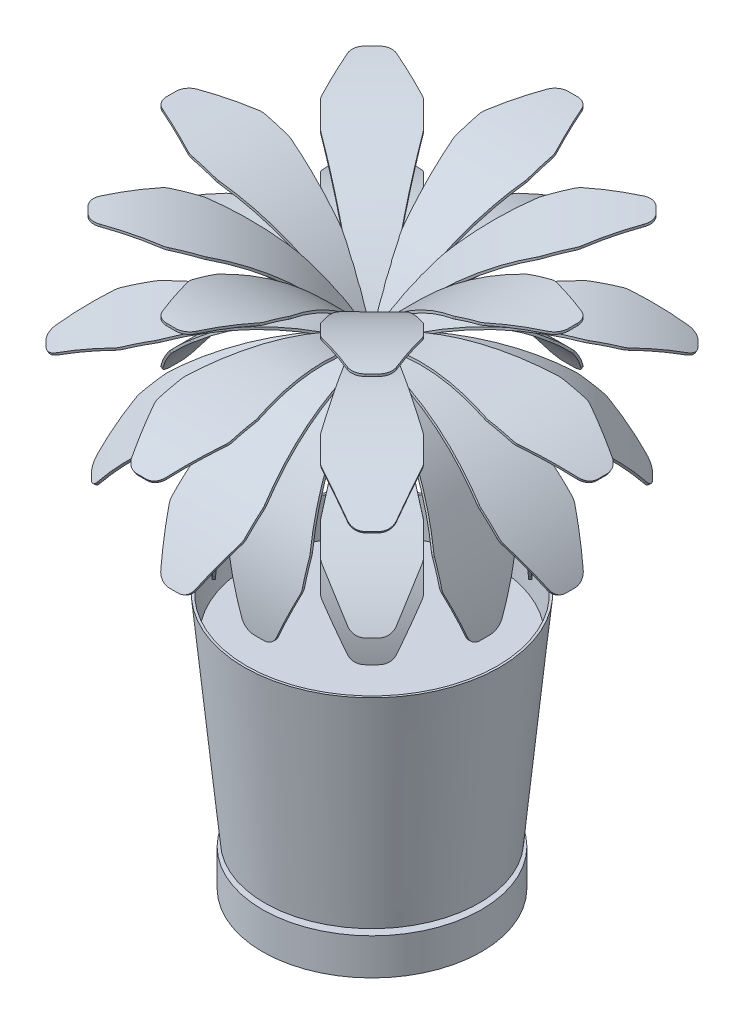
SolidWorks part; units mm, degrees
note: '?' marks a value the reader was unsure of.
material "Beech"
ref_plane "Front Plane" through (0, 0, 0) normal (0, 0, 1) x (1, 0, 0)
ref_plane "Top Plane" through (0, 0, 0) normal (0, 1, 0) x (1, 0, 0)
ref_plane "Right Plane" through (0, 0, 0) normal (1, 0, 0) x (0, 0, -1)
ref_axis "X-Axis" through (-88.99, 0, 0) along (1, 0, 0)?
ref_axis "Y-Axis" through (0, 55, 0) along (0, -1, 0)?
ref_axis "Z-Axis" through (0, 0, -88.99) along (0, 0, 1)?
sketch "Sketch1" plane through (0, 0, 0) normal (0, 0, 1) x (1, 0, 0)
  line L0 (0, 0) -> (0, 152.4)
  line L1 (87.3052, 177.8) -> (88.9, 177.8)
  line L2 (88.9, 177.8) -> (74.6125, 28.575)
  line L3 (74.6125, 28.575) -> (69.85, 28.575)
  line L4 (69.85, 28.575) -> (69.85, 25.4)
  line L5 (69.85, 25.4) -> (76.2, 25.4)
  line L6 (76.2, 25.4) -> (76.2, 0)
  line L7 (76.2, 0) -> (0, 0)
  line L8 (0, 0) -> (0, -76.2) construction
  line L9 (87.3052, 177.8) -> (84.8733, 152.4)
  line L10 (84.8733, 152.4) -> (0, 152.4)
  dimension "D1" = 25.4
  dimension "D2" = 177.8
  dimension "D3" = 152.4
  dimension "D4" = 6.35
  dimension "D5" = 3.175
  dimension "D6" = 1.5875
  dimension "D7" = 177.8
  dimension "D8" = 25.4
  dimension "D9" = 1.5875
revolve "Revolve1" add sketch "Sketch1" angle 360 about L8
sketch "Sketch3" plane through (0, 152.4, 0) normal (0, 1, 0) x (1, 0, 0)
  circle A0 centre (0, 0) radius 9.525
  dimension "D1" = 19.05
extrude "Boss-Extrude1" add sketch "Sketch3" along normal blind 177.8 draft 2 separate body
sketch "Sketch4" plane through (0, 0, 0) normal (0, 0, 1) x (1, 0, 0)
  line L0 (3.3161, 330.2) -> (-3.3161, 330.2) construction
  line L1 (77.1118, 190.5) -> (78.6993, 190.5)
  line L2 (0.846, 331.5433) -> (0, 330.2)
  line L3 (87.3052, 177.8) -> (-87.3052, 177.8) construction
  arc A0 (0, 330.2) -> (77.1118, 190.5) centre (-87.9882, 190.5) cw
  arc A1 (78.6993, 190.5) -> (0.846, 331.5433) centre (-87.9882, 190.5) ccw
  dimension "D2" = 165.1
  dimension "D1" = 1.5875
  dimension "D3" = 12.7
extrude "Boss-Extrude2" add sketch "Sketch4" along normal mid plane 50.8 separate body
sketch "Sketch5" plane through (0, 0, 0) normal (1, 0, 0) x (0, 0, -1)
  line L0 (-9.525, 190.5) -> (-25.4, 228.6)
  line L1 (-25.4, 331.5433) -> (-25.4, 190.5) construction
  line L2 (-25.4, 228.6) -> (-25.4, 247.65)
  line L3 (-25.4, 247.65) -> (-6.35, 331.5433)
  line L4 (-25.4, 331.5433) -> (25.4, 331.5433) construction
  line L5 (-6.35, 331.5433) -> (6.35, 331.5433)
  line L6 (6.35, 331.5433) -> (25.4, 247.65)
  line L7 (25.4, 190.5) -> (25.4, 331.5433) construction
  line L8 (25.4, 247.65) -> (25.4, 228.6)
  line L9 (25.4, 228.6) -> (9.525, 190.5)
  line L10 (-25.4, 190.5) -> (25.4, 190.5) construction
  line L11 (-9.525, 190.5) -> (9.525, 190.5)
  line L12 (0, 190.5) -> (0, 0) construction
  dimension "D1" = 19.05
  dimension "D2" = 19.05
  dimension "D3" = 38.1
  dimension "D4" = 12.7
extrude "Cut-Extrude1" cut sketch "Sketch5" along normal through all flip side to cut
fillet "Fillet6" radius 9.525 6 edges at (73.4711, 228.6, 25.4) (67.7505, 247.65, 25.4) (67.7505, 247.65, -25.4) (73.4711, 228.6, -25.4) (77.9056, 190.5, 9.525) (77.9056, 190.5, -9.525)
pattern_circular "CirPattern2" count 4 every 30 about axis through (0, 330.2, 0) along (0, 0, 1) of bodies 104
pattern_circular "CirPattern3" count 8 over 360 about axis through (0, 0, 0) along (0, 1, 0) of bodies 107 106 105 104
scale "Scale2" bodies to scale 120 129 102 112 121 130 101 113 131 122 132 114 104 123 133 105 115 124 134 106 116 125 135 107 108 117 126 109 118 127 110 119 128 111 scale about origin uniform scaling yes scale factor 0.322034
